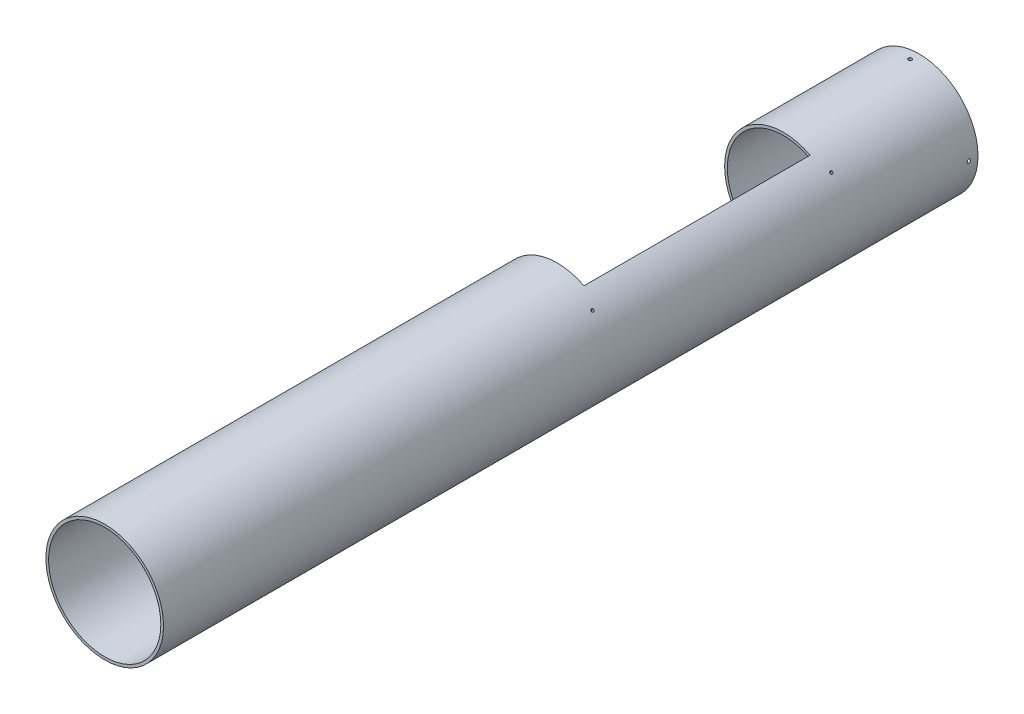
SolidWorks part; units mm, degrees
ref_plane "Front Plane" through (0, 0, 0) normal (0, 0, 1) x (1, 0, 0)
ref_plane "Top Plane" through (0, 0, 0) normal (0, 1, 0) x (1, 0, 0)
ref_plane "Right Plane" through (0, 0, 0) normal (1, 0, 0) x (0, 0, -1)
sketch "Sketch1" plane through (0, 0, 0) normal (0, 0, 1) x (1, 0, 0)
  circle A0 centre (0, 0) radius 62
  circle A1 centre (0, 0) radius 65
  dimension "D1" = 124
  dimension "D2" = 3
extrude "Boss-Extrude1" add sketch "Sketch1" along normal blind 900
sketch "Sketch2" plane through (0, 0, 0) normal (0, 1, 0) x (1, 0, 0)
  line L0 (62, 0) -> (-62, 0) construction
  circle A0 centre (0, -224) radius 1
  circle A1 centre (0, -264) radius 1
  dimension "D1" = 2
  dimension "D3" = 2
  dimension "D2" = 224
  dimension "D4" = 40
ref_plane "Plane1" through (0, 0, 0) normal (-0.7071, 0.7071, 0) x (0.7071, 0.7071, 0)
ref_plane "Plane2" through (-14.1421, 14.1421, 0) normal (-0.7071, 0.7071, 0) x (0.7071, 0.7071, 0)
sketch "Sketch4" plane through (-14.1421, 14.1421, 0) normal (-0.7071, 0.7071, 0) x (0.7071, 0.7071, 0)
  line L0 (-65, 0) -> (-65, -900) construction
  line L1 (-65, -150) -> (65, -150)
  line L2 (-65, -150) -> (-65, -400)
  line L3 (-65, -400) -> (65, -400)
  line L4 (65, -150) -> (65, -400)
  line L5 (65, -900) -> (65, 0) construction
  line L6 (65, 0) -> (-65, 0) construction
  dimension "D1" = 150
  dimension "D2" = 250
extrude "Cut-Extrude4" cut sketch "Sketch4" along normal blind 516
sketch "Sketch5" plane through (0, 0, 0) normal (0, 1, 0) x (1, 0, 0)
  line L0 (-62, 0) -> (62, 0) construction
  circle A0 centre (0, -10) radius 2
  dimension "D1" = 4
  dimension "D2" = 10
extrude "Cut-Extrude5" cut sketch "Sketch5" against normal blind 85
pattern_circular "CirPattern1" count 4 every 90 about axis through (0, 0, 900) along (0, 0, -1) of "Cut-Extrude5"
sketch "Sketch7" plane through (-14.1421, 14.1421, 0) normal (-0.7071, 0.7071, 0) x (0.7071, 0.7071, 0)
  line L0 (-61.8466, -150) -> (61.8466, -150) construction
  line L1 (58.6856, -400) -> (-58.6856, -400) construction
  circle A0 centre (0, -143) radius 1.5
  circle A1 centre (0, -407) radius 1.5
  dimension "D1" = 3
  dimension "D3" = 3
  dimension "D2" = 7
  dimension "D4" = 7
extrude "Cut-Extrude6" cut sketch "Sketch7" along normal blind 243
pattern_circular "CirPattern2" count 4 every 90 about axis through (0, 0, 900) along (0, 0, -1) of "Cut-Extrude6"
